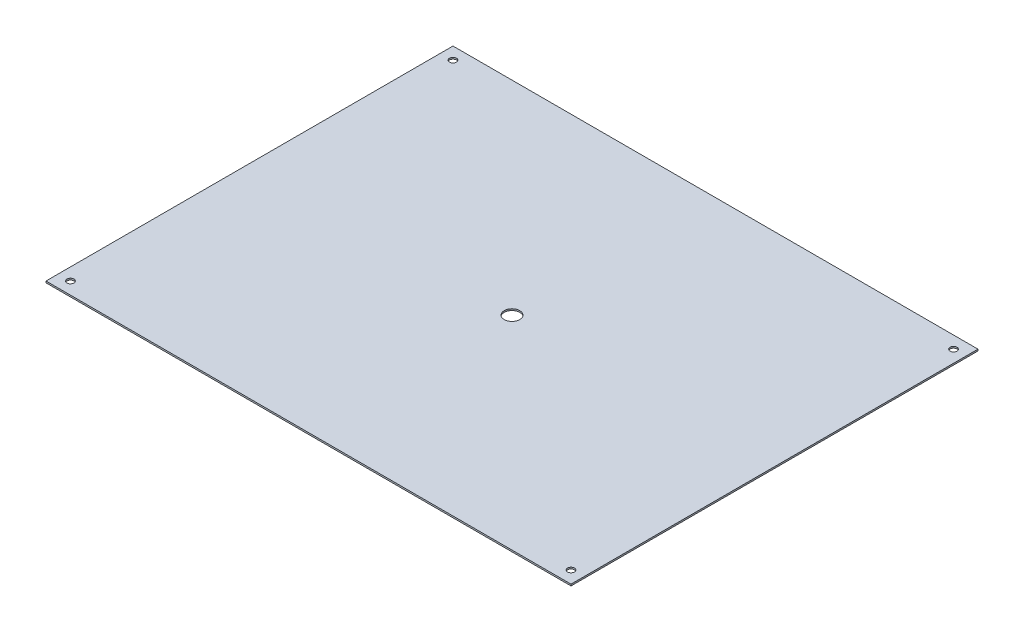
SolidWorks part; units mm, degrees
ref_plane "Front Plane" through (0, 0, 0) normal (0, 0, 1) x (1, 0, 0)
ref_plane "Top Plane" through (0, 0, 0) normal (0, 1, 0) x (1, 0, 0)
ref_plane "Right Plane" through (0, 0, 0) normal (1, 0, 0) x (0, 0, -1)
sketch "Sketch1" plane through (0, 0, 0) normal (0, 0, 1) x (1, 0, 0)
  line L0 (0, 0.3969) -> (0, -0.3969)
  line L1 (-152.4, 0) -> (152.4, 0) construction
  point P6 (0, 0)
  dimension "Width" = 304.8
  dimension "Thk" = 0.7937
sketch "Sketch2" plane through (0, 0, 0) normal (1, 0, 0) x (0, 0, -1)
  line L0 (152.4, 0) -> (-152.4, 0)
  point P4 (0, 0)
  dimension "Length" = 304.8
sketch "Sketch3" plane through (0, 0, 0) normal (0, 0, 1) x (1, 0, 0)
  line L1 (152.4, 0.3969) -> (-152.4, 0.3969)
  line L2 (152.4, 0.3969) -> (152.4, -0.3969)
  line L3 (152.4, -0.3969) -> (-152.4, -0.3969)
  line L4 (-152.4, 0.3969) -> (-152.4, -0.3969)
  line L5 (152.4, 0.3969) -> (-152.4, -0.3969) construction
  line L6 (152.4, -0.3969) -> (-152.4, 0.3969) construction
  point P0 (0, 0)
extrude "Boss-Extrude1" add sketch "Sketch3" along normal up to vertex (152.4 mm away) and the other way up to vertex (152.4 mm away) up to point (0, 0, 152.4) other way up to point (0, 0, -152.4)
sketch "Sketch4" plane through (0, 0.3969, 0) normal (0, 1, 0) x (1, 0, 0)
  line L1 (-129, 100) -> (129, 100)
  line L2 (-129, 100) -> (-129, -100)
  line L3 (-129, -100) -> (129, -100)
  line L4 (129, 100) -> (129, -100)
  line L5 (-129, 100) -> (-129, -100) construction
extrude "Fit2Enclosure" cut sketch "Sketch4" against normal up to next (0.7937 mm away) flip side to cut
hole_wizard "CubeMountHoles" positions "Sketch6" profile "Sketch7" hole size "M3" standard "ANSI Metric" end condition up to next
sketch "Sketch6" plane through (0, 0.3969, 0) normal (0, 1, 0) x (1, 0, 0)
  point P0 (-123, 94)
  point P3 (123, 94)
  point P6 (123, -94)
  point P9 (-122.975, -94)
sketch "Sketch7" plane through (-123, 0.3969, -94) normal (1, 0, 0) x (0, 0, 1)
  line L0 (0, 0) -> (0, 0.7937)
  line L1 (0, 0.7937) -> (1.7, 0.7937)
  line L2 (1.7, 0.7937) -> (1.7, 0)
  line L5 (1.7, 0) -> (0, 0)
  line L11 (0, -6.35) -> (0, 107.95) construction
  dimension "Thru Hole Dia." = 3.4
  dimension "Thru Hole Depth" = 0.7938
sketch "Sketch8" plane through (0, 0.3969, 0) normal (0, 1, 0) x (1, 0, 0)
  line L1 (0, 465.5803) -> (0, 325.8803) construction
  line L2 (-188.8422, 0) -> (-49.1422, 0) construction
  circle A0 centre (0, 0) radius 3.81
  dimension "D1" = 7.62
extrude "DrainHole" cut sketch "Sketch8" against normal up to next
ref_plane "SheetTop" through (0, 0.3969, 0) normal (0, 1, 0) x (1, 0, 0)
ref_plane "SheetBottom" through (0, -0.3969, 0) normal (0, -1, 0) x (-1, 0, 0)
ref_axis "DrainHoleAxis" through (0, -0.3969, 0) along (0, 1, 0)
ref_axis "Mnt1" through (-123, -0.3969, -94) along (0, 1, 0)
ref_axis "Mnt2" through (123, -0.3969, -94) along (0, 1, 0)
ref_axis "Mnt3" through (123, -0.3969, 94) along (0, 1, 0)
ref_axis "Mnt4" through (-122.975, -0.3969, 94) along (0, 1, 0)
